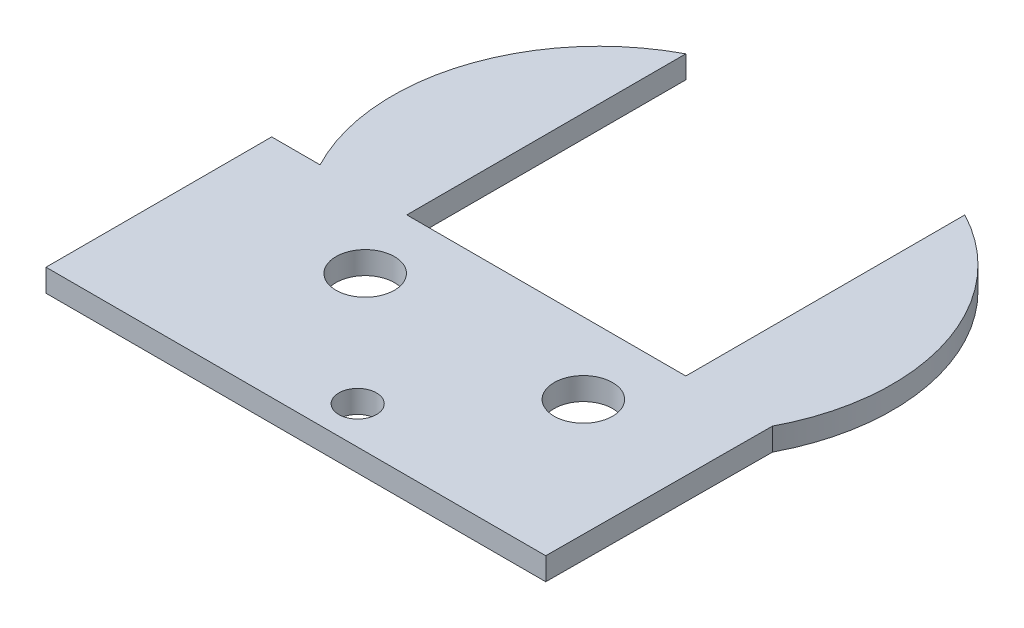
SolidWorks part; units mm, degrees
ref_plane "Front Plane" through (0, 0, 0) normal (0, 0, 1) x (1, 0, 0)
ref_plane "Top Plane" through (0, 0, 0) normal (0, 1, 0) x (1, 0, 0)
ref_plane "Right Plane" through (0, 0, 0) normal (1, 0, 0) x (0, 0, -1)
sketch "Sketch1" plane through (0, 0, 0) normal (0, 1, 0) x (1, 0, 0)
  line L2 (17.3158, 0) -> (17.3158, 37.0896)
  line L3 (-19.7738, 0) -> (17.3158, 0)
  line L7 (-37.7335, -30) -> (28.6983, -30)
  line L8 (-1.229, 0) -> (-1.229, 58.2334) construction
  line L9 (28.6983, -30) -> (28.8436, 0)
  line L12 (-37.7335, -30) -> (-37.7335, 0)
  line L13 (-19.7738, 0) -> (-19.7738, 37.0896)
  line L14 (-37.7335, 0) -> (-31.3017, 0)
  arc A5 (17.3158, 37.0896) -> (28.8436, 0) centre (4.5349, 12.7809) cw
  arc A6 (-19.7738, 37.0896) -> (-31.3017, 0) centre (-6.993, 12.7809) ccw
extrude "Boss-Extrude1" add sketch "Sketch1" along normal blind 3
sketch "Sketch2" plane through (0, 3, 0) normal (0, 1, 0) x (1, 0, 0)
  line L0 (-1.3017, -45) -> (-1.3017, -5) construction
  circle A1 centre (-1.3017, -25) radius 2.5
extrude "Cut-Extrude1" cut sketch "Sketch2" against normal blind 20
sketch "Sketch3" plane through (0, 0, 0) normal (0, -1, 0) x (1, 0, 0)
  line L0 (28.6983, 30) -> (28.8436, 0) construction
  line L1 (15.6983, 7) -> (10.6983, 7)
  line L2 (15.6983, 7) -> (15.6983, 12)
  line L3 (15.6983, 12) -> (10.6983, 12)
  line L4 (10.6983, 7) -> (10.6983, 12)
  line L6 (-1.1567, 0.0007) -> (-1.3747, 45.0002) construction
  line L8 (-13.079, 6.8848) -> (-13.1275, 11.8846)
  line L9 (-18.1272, 11.8361) -> (-13.1275, 11.8846)
  line L10 (-18.0788, 6.8364) -> (-18.1272, 11.8361)
  line L11 (-18.0788, 6.8364) -> (-13.079, 6.8848)
  dimension "D4" = 30
extrude "Cut-Extrude2" cut sketch "Sketch3" against normal blind 10
sketch "Sketch4" plane through (0, 0, 0) normal (0, -1, 0) x (1, 0, 0)
  line L0 (13.1983, 7) -> (13.1983, 12) construction
  line L1 (10.6983, 7) -> (15.6983, 7) construction
  line L2 (15.6983, 12) -> (10.6983, 12) construction
  line L3 (15.6983, 9.5) -> (10.6983, 9.5) construction
  line L4 (15.6983, 7) -> (15.6983, 12) construction
  line L5 (10.6983, 12) -> (10.6983, 7) construction
  circle A0 centre (13.1983, 9.5) radius 3.8814
  circle A1 centre (-15.8017, 9.5) radius 3.8814
extrude "Cut-Extrude3" cut sketch "Sketch4" against normal blind 10
sketch "Sketch5" plane through (0, 3, 0) normal (0, 1, 0) x (1, 0, 0)
  line L0 (-7.7335, 0) -> (-7.7335, -17) construction
  line L2 (14.2665, -17) -> (-29.7335, -17) construction
  circle A0 centre (-5.7817, -9.5) radius 3
  circle A1 centre (-9.6854, -9.5) radius 3
  point P5 (0, 0)
  dimension "D1" = 6
  dimension "D2" = 0
  dimension "D3" = 10.02
extrude "Cut-Extrude4" cut sketch "Sketch5" against normal blind 10 rebuild error yes
